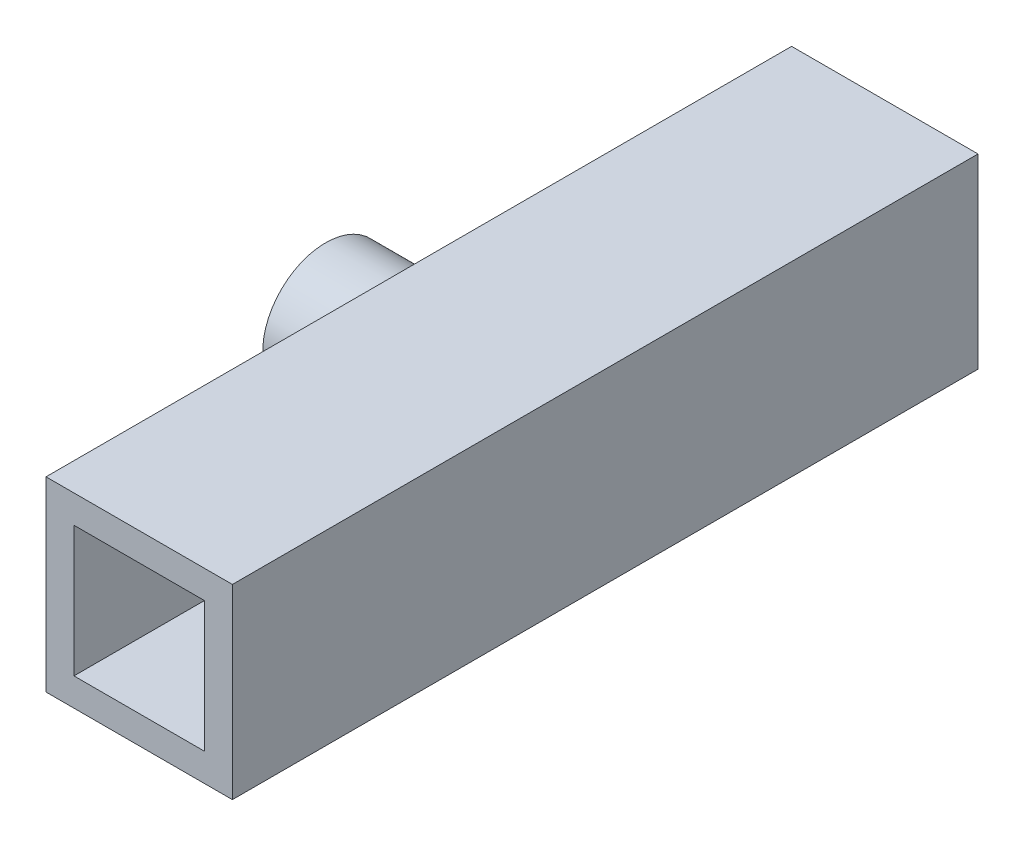
SolidWorks part; units mm, degrees
ref_plane "Front Plane" through (0, 0, 0) normal (0, 0, 1) x (1, 0, 0)
ref_plane "Top Plane" through (0, 0, 0) normal (0, 1, 0) x (1, 0, 0)
ref_plane "Right Plane" through (0, 0, 0) normal (1, 0, 0) x (0, 0, -1)
sketch "Sketch1" plane through (0, 0, 0) normal (0, 0, 1) x (1, 0, 0)
  line L1 (-10, -10) -> (10, -10)
  line L2 (-10, -10) -> (-10, 10)
  line L3 (-10, 10) -> (10, 10)
  line L4 (10, -10) -> (10, 10)
  line L5 (-10, -10) -> (10, 10) construction
  line L6 (-10, 10) -> (10, -10) construction
  point P0 (0, 0)
  dimension "D1" = 20
  dimension "D2" = 20
extrude "Boss-Extrude1" add sketch "Sketch1" along normal blind 80
shell "Shell1" thickness 3 removed face at (0, 0, 0) removed face at (0, 0, 80)
sketch "Sketch2" plane through (10, 0, 0) normal (1, 0, 0) x (0, 0, -1)
  circle A0 centre (-40, 0) radius 6.75
  dimension "D1" = 13.5
  dimension "D2" = 40
extrude "Boss-Extrude2" add sketch "Sketch2" against normal blind 10 from surface starting at face at (-10, 0, 40)
